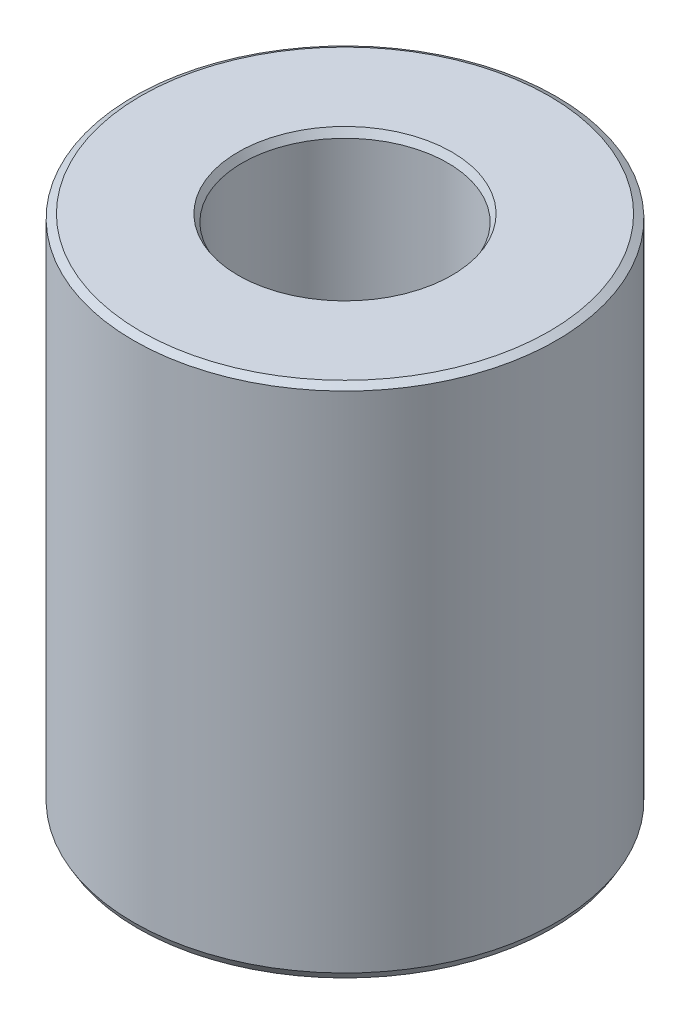
SolidWorks part; units mm, degrees
ref_plane "Front Plane" through (0, 0, 0) normal (0, 0, 1) x (1, 0, 0)
ref_plane "Top Plane" through (0, 0, 0) normal (0, 1, 0) x (1, 0, 0)
ref_plane "Right Plane" through (0, 0, 0) normal (1, 0, 0) x (0, 0, -1)
sketch "Sketch1" plane through (0, 0, 0) normal (0, 1, 0) x (1, 0, 0)
  circle A0 centre (0, 0) radius 20
  dimension "SLEEVE_OD" = 40
extrude "Boss-Extrude1" add sketch "Sketch1" along normal blind 48.7776
sketch "Sketch2" plane through (0, 0, 0) normal (0, 1, 0) x (1, 0, 0)
  circle A0 centre (0, 0) radius 9.7149
  dimension "BORE_D" = 19.4297
extrude "Cut-Extrude1" cut sketch "Sketch2" along normal through all
chamfer "Chamfer1" distance 0.3978 angle 60 4 edges at (0, 48.7776, 9.7149) (0, 0, 9.7149) (0, 0, 20) (0, 48.7776, 20) first distance on face at (0, 48.7776, 9.7149) first distance on face at (0, 0, 9.7149) first distance on face at (0, 48.7776, 20)
